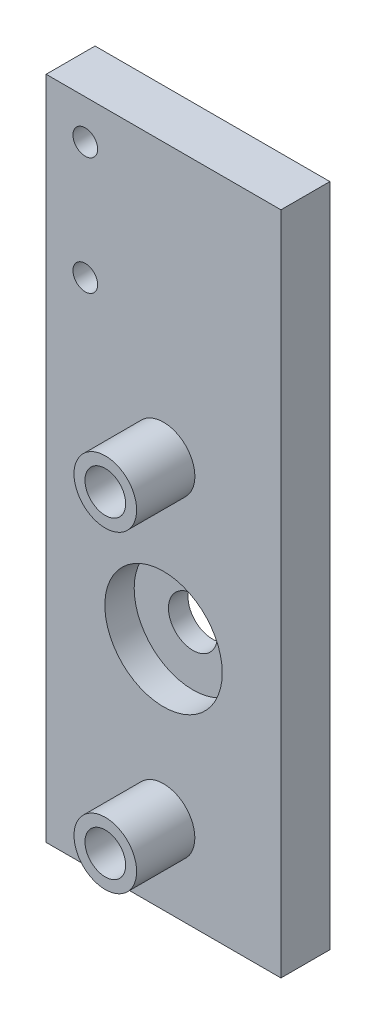
SolidWorks part; units mm, degrees
ref_plane "Front Plane" through (0, 0, 0) normal (0, 0, 1) x (1, 0, 0)
ref_plane "Top Plane" through (0, 0, 0) normal (0, 1, 0) x (1, 0, 0)
ref_plane "Right Plane" through (0, 0, 0) normal (1, 0, 0) x (0, 0, -1)
sketch "Sketch1" plane through (0, 0, 0) normal (0, 0, 1) x (1, 0, 0)
  line L1 (-19.05, -38.1) -> (19.05, -38.1)
  line L2 (-19.05, -38.1) -> (-19.05, 38.1)
  line L3 (-19.05, 38.1) -> (19.05, 38.1)
  line L4 (19.05, -38.1) -> (19.05, 38.1)
  line L5 (-19.05, -38.1) -> (19.05, 38.1) construction
  line L6 (-19.05, 38.1) -> (19.05, -38.1) construction
  point P0 (0, 0)
  dimension "D1" = 38.1
  dimension "D2" = 76.2
extrude "Boss-Extrude1" add sketch "Sketch1" along normal blind 7.9375
sketch "Sketch2" plane through (0, 0, 7.9375) normal (0, 0, 1) x (1, 0, 0)
  circle A0 centre (0, 0) radius 3.9688
  dimension "D1" = 7.9375
extrude "Cut-Extrude1" cut sketch "Sketch2" against normal through all
sketch "Sketch4" plane through (0, 0, 7.9375) normal (0, 0, 1) x (1, 0, 0)
  circle A0 centre (0, 0) radius 9.525
  dimension "D1" = 19.05
extrude "Cut-Extrude2" cut sketch "Sketch4" against normal offset from surface (4.7625 mm away) 3.175 up to face at (3.9688, 0, 0)
sketch "Sketch5" plane through (0, 0, 7.9375) normal (0, 0, 1) x (1, 0, 0)
  line L0 (19.05, 38.1) -> (-19.05, 38.1) construction
  circle A0 centre (0, 25.4) radius 5.08
  dimension "D1" = 10.16
  dimension "D2" = 12.7
extrude "Boss-Extrude2" add sketch "Sketch5" along normal blind 9.4488
sketch "Sketch6" plane through (0, 0, 17.3863) normal (0, 0, 1) x (1, 0, 0)
  circle A0 centre (0, 25.4) radius 3.302
  dimension "D1" = 6.604
extrude "Cut-Extrude3" cut sketch "Sketch6" against normal through all
mirror "Mirror1" about plane through (0, 0, 0) normal (0, 1, 0) of "Cut-Extrude3", "Boss-Extrude2"
sketch "Sketch7" plane through (0, 0, 7.9375) normal (0, 0, 1) x (1, 0, 0)
  line L1 (-19.05, 38.1) -> (19.05, 38.1)
  line L2 (-19.05, 38.1) -> (-19.05, 69.85)
  line L3 (-19.05, 69.85) -> (19.05, 69.85)
  line L4 (19.05, 38.1) -> (19.05, 69.85)
  line L5 (19.05, -38.1) -> (19.05, 38.1) construction
  line L6 (-19.05, 53.975) -> (19.05, 53.975) construction
  line L7 (-12.7, 69.85) -> (-12.7, 38.1) construction
  circle A0 centre (-12.7, 63.5) radius 2
  circle A1 centre (-12.7, 44.45) radius 2
  dimension "D3" = 4
  dimension "D1" = 31.75
  dimension "D2" = 6.35
  dimension "D4" = 9.525
extrude "Boss-Extrude4" add sketch "Sketch7" against normal up to surface (7.9375 mm away) up to face at (3.302, -25.4, 0)
